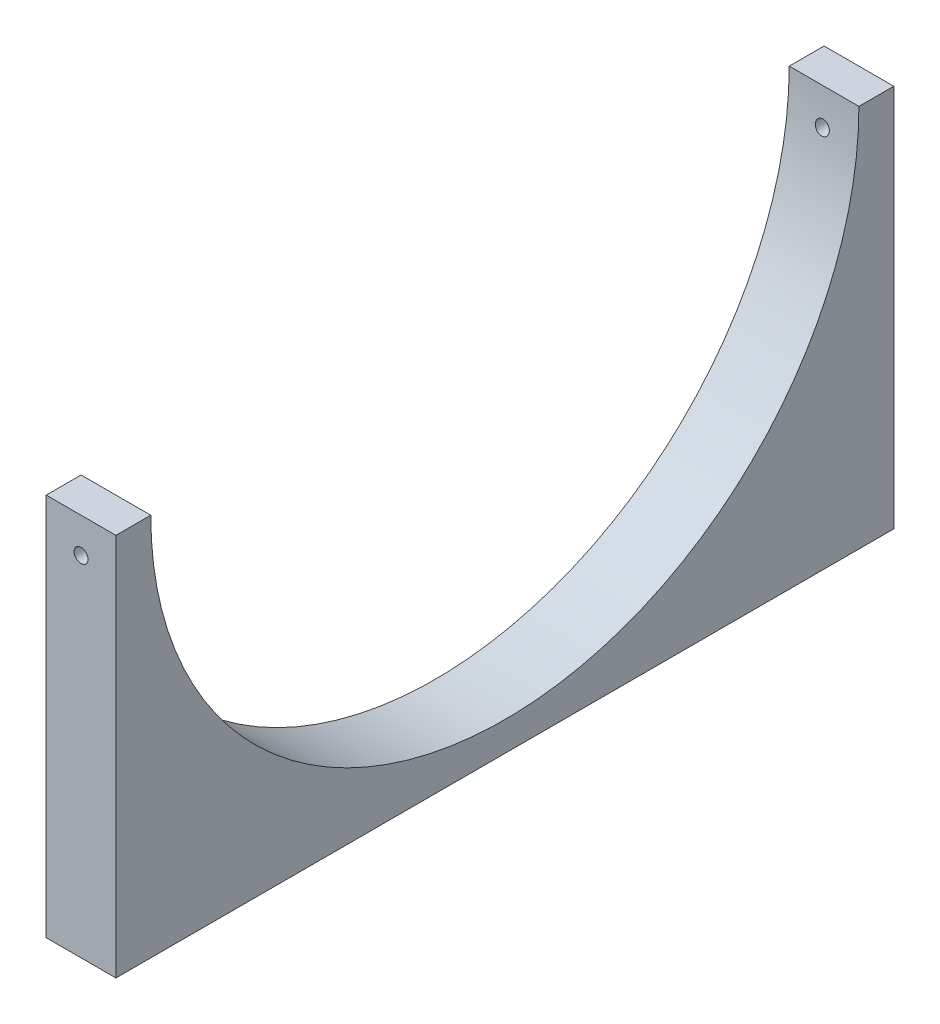
SolidWorks part; units mm, degrees
material "1060 Alloy"
ref_plane "Front Plane" through (0, 0, 0) normal (0, 0, 1) x (1, 0, 0)
ref_plane "Top Plane" through (0, 0, 0) normal (0, 1, 0) x (1, 0, 0)
ref_plane "Right Plane" through (0, 0, 0) normal (1, 0, 0) x (0, 0, -1)
sketch "Sketch1" plane through (0, 0, 0) normal (0, 1, 0) x (1, 0, 0)
  line L1 (-68.4091, -57.85) -> (121.0909, -57.85)
  line L2 (-68.4091, -57.85) -> (-68.4091, 53.75)
  line L3 (-68.4091, 53.75) -> (121.0909, 53.75)
  line L4 (121.0909, -57.85) -> (121.0909, 53.75)
  dimension "D1" = 111.6
  dimension "D2" = 189.5
extrude "Boss-Extrude1" add sketch "Sketch1" along normal blind 80
sketch "Sketch3" plane through (0, 0, 57.85) normal (0, 0, 1) x (1, 0, 0)
  line L0 (-68.4091, 0) -> (121.0909, 0) construction
  line L1 (-68.4091, 80) -> (-68.4091, 0) construction
  circle A0 centre (-6.7091, 45) radius 8.15
  circle A1 centre (44.2909, 45) radius 8.15
  circle A2 centre (95.2909, 45) radius 8.15
  dimension "D1" = 16.3
  dimension "D2" = 16.3
  dimension "D3" = 16.3
  dimension "D5" = 0
  dimension "D7" = 51
  dimension "D8" = 51
  dimension "D9" = 61.7
  dimension "D4" = 45
  dimension "D6" = 0
extrude "Cut-Extrude2" cut sketch "Sketch3" against normal blind 40
sketch "Sketch4" plane through (0, 0, -53.75) normal (0, 0, -1) x (-1, 0, 0)
  line L0 (68.4091, 0) -> (-121.0909, 0) construction
  circle A0 centre (-18.7909, 45) radius 10.3
  circle A1 centre (-44.2909, 45) radius 8.15 construction
  dimension "D1" = 20.6
  dimension "D2" = 25.5
  dimension "D3" = 45
extrude "Cut-Extrude3" cut sketch "Sketch4" against normal blind 40
sketch "Sketch2" plane through (-68.4091, 0, 0) normal (-1, 0, 0) x (0, 0, 1)
  line L0 (57.85, 80) -> (57.85, 0) construction
  line L1 (-53.75, 0) -> (57.85, 0) construction
  line L2 (-101.4382, 55) -> (76.5005, 55)
  line L3 (-48.75, 55) -> (52.85, 55)
  line L4 (-48.75, 55) -> (-48.75, 118.783)
  line L5 (-48.75, 118.783) -> (52.85, 118.783)
  line L6 (52.85, 55) -> (52.85, 118.783)
  line L7 (-91.5671, 45) -> (56.581, 45)
  circle A0 centre (2.05, 55) radius 50.8
  line M2 (57.85, 0) -> (57.85, 80)
  line M3 (57.85, 80) -> (-53.75, 80)
  line M4 (-53.75, 80) -> (-53.75, 0)
  dimension "D1" = 101.6
  dimension "D2" = 55.8
  dimension "D3" = 55
  dimension "D4" = 101.6
  dimension "D5" = 10
extrude "Cut-Extrude1" cut sketch "Sketch2" against normal through all contours L2 A0 M3 | A0 L4 M3 | L2 A0 | A0 L6 M3 | L2 L4 M3 M4 | L6 L2 M2 M3 | L7 A0 region at (-68.4091, 67.2225, 2.05) region at (-68.4091, 67.5, -51.25) region at (-68.4091, 73.8338, -46.8008) region at (-68.4091, 50.0164, 2.05) region at (-68.4091, 67.5, 55.35) region at (-68.4091, 73.8338, 50.9008) region at (-68.4091, 27.9434, 2.05)
sketch "Sketch5" plane through (-68.4091, 0, 0) normal (-1, 0, 0) x (0, 0, 1)
  circle A0 centre (5.8994, 41.151) radius 83.6376
extrude "Cut-Extrude5" cut sketch "Sketch5" against normal through all from offset 10 offset against normal yes
sketch "Sketch6" plane through (0, 0, 0) normal (0, -1, 0) x (1, 0, 0)
  line L0 (-58.4091, 57.85) -> (-58.4091, -53.75) construction
  line L1 (-68.4091, 57.85) -> (-58.4091, 57.85) construction
  line L2 (-58.4091, -53.75) -> (-68.4091, -53.75) construction
  circle A0 centre (-63.4091, 42.85) radius 2
  circle A1 centre (-63.4091, -38.75) radius 2
  dimension "D1" = 4
  dimension "D2" = 4
  dimension "D6" = 15
  dimension "D3" = 5
  dimension "D4" = 5
  dimension "D5" = 15
extrude "Cut-Extrude6" cut sketch "Sketch6" against normal blind 15
sketch "Sketch7" plane through (0, 0, 57.85) normal (0, 0, 1) x (1, 0, 0)
  line L0 (-58.4091, 0) -> (-58.4091, 55) construction
  line L1 (-58.4091, 55) -> (-68.4091, 55) construction
  circle A0 centre (-63.4091, 50) radius 1
  dimension "D1" = 2
  dimension "D2" = 5
  dimension "D3" = 5
extrude "Cut-Extrude7" cut sketch "Sketch7" against normal through all both and the other way through all
